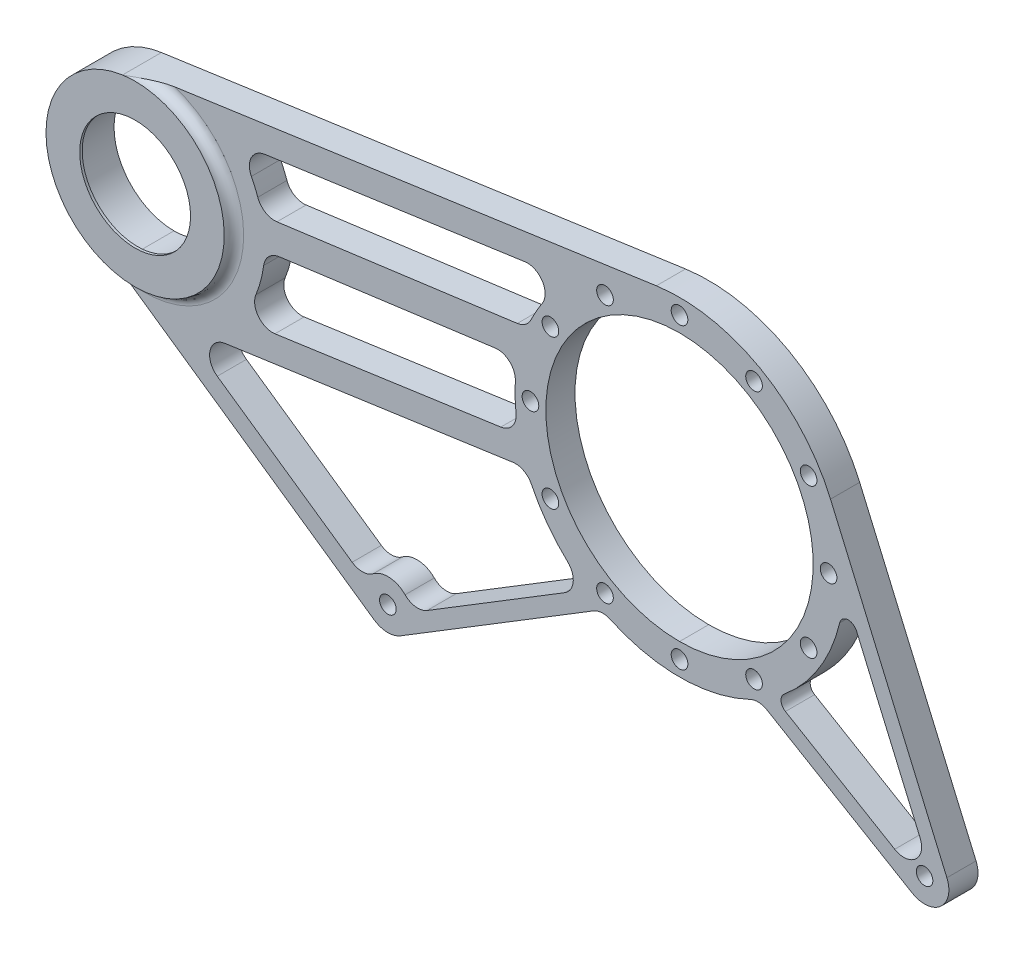
SolidWorks part; units mm, degrees
material "6061-T6 (SS)"
ref_plane "Front Plane" through (0, 0, 0) normal (0, 0, 1) x (1, 0, 0)
ref_plane "Top Plane" through (0, 0, 0) normal (0, 1, 0) x (1, 0, 0)
ref_plane "Right Plane" through (0, 0, 0) normal (1, 0, 0) x (0, 0, -1)
sketch "Sketch1" plane through (0, 0, 0) normal (0, 0, 1) x (1, 0, 0)
  line L0 (-328.7713, 136.1765) -> (-123.3819, 165.4094)
  line L1 (-343.7594, 72.9056) -> (-234.0298, -3.2296)
  line L2 (-223.6277, -3.528) -> (-148.0091, 42.7538)
  line L3 (-114.3, 88.9) -> (-114.3, 101.6) construction
  line L4 (-55.1193, 127.1299) -> (-9.5189, 21.4239)
  line L5 (-23.1153, 9.4535) -> (-80.0139, 43.1208)
  circle A0 centre (-114.3, 88.9) radius 82.9716 construction
  circle A1 centre (-228.6, -20.8038) radius 12.7 construction
  circle A2 centre (0, 0) radius 12.7 construction
  circle A3 centre (-323.85, 101.6) radius 114 construction
  circle A4 centre (-323.85, 101.6) radius 23.5
  circle A5 centre (-114.3, 101.6) radius 52.3875
  arc A6 (-141.4233, 43.1325) -> (-86.5756, 43.4151) centre (-114.3, 101.6) ccw
  circle A7 centre (-323.85, 101.6) radius 34.925
  arc A8 (-223.6277, -3.528) -> (-234.0298, -3.2296) centre (-228.6, 4.5962) cw
  arc A9 (-9.5189, 21.4239) -> (-23.1153, 9.4535) centre (-18.2648, 17.651) cw
  circle A10 centre (-228.6, 4.5962) radius 3.2512
  circle A11 centre (-18.2648, 17.651) radius 3.2512
  arc A12 (-141.4233, 43.1325) -> (-148.0091, 42.7538) centre (-144.3627, 36.7961) ccw
  arc A13 (-80.0139, 43.1208) -> (-86.5756, 43.4151) centre (-83.571, 37.1094) ccw
  arc A14 (-141.4233, 43.1325) -> (-86.5756, 43.4151) centre (-114.3, 101.6) ccw construction
  arc A15 (-123.3819, 165.4094) -> (-55.1193, 127.1299) centre (-114.3, 101.6) cw
  arc A16 (-141.4233, 43.1325) -> (-86.5756, 43.4151) centre (-114.3, 101.6) ccw
  arc A17 (-55.1193, 127.1299) -> (-123.3819, 165.4094) centre (-114.3, 101.6) ccw construction
  point P32 (0, 0)
  point P33 (0, 0)
  dimension "D1" = 88.9
  dimension "D2" = 12.7
  dimension "D3" = 25.4
  dimension "D4" = 25.4
  dimension "D8" = 165.9433
  dimension "D9" = 228
  dimension "D10" = 47
  dimension "D12" = 104.775
  dimension "D15" = 69.85
  dimension "D16" = 9.525
  dimension "D18" = 9.525
  dimension "D20" = 6.5024
  dimension "D21" = 6.5024
  dimension "D23" = 6.985
  dimension "D24" = 6.985
  dimension "D25" = 128.905
  dimension "D5" = 228.6
  dimension "D6" = 20.8038
  dimension "D7" = 114.3
  dimension "D11" = 12.7
  dimension "D13" = 209.55
  dimension "D17" = 25.4
  dimension "D19" = 25.4
  dimension "D22" = 17.651
extrude "Boss-Extrude1" add sketch "Sketch1" along normal blind 11.43 contours A7 A4 | A8 L2 A6 L0 A7 L1 A10 | A6 A5 | A9 L4 A6 L5 A11 region at (-188.8604, 80.9757, 0) region at (-301.6077, 127.2322, 0)
ref_point "Point2"
ref_point "Point4"
ref_plane "Plane2" through (-114.3, 0, 0) normal (1, 0, 0) x (0, 0, -1)
ref_plane "Plane3" through (-323.85, 0, 0) normal (1, 0, 0) x (0, 0, -1)
sketch "Sketch5" plane through (0, 0, 11.43) normal (0, 0, 1) x (1, 0, 0)
  circle A0 centre (-323.85, 101.6) radius 23.5
  circle A1 centre (-323.85, 101.6) radius 34.925
extrude "Boss-Extrude3" add sketch "Sketch5" along normal blind 3.81
fillet "Fillet2" radius 3.81 1 edges at (-289.8655, 93.5495, 11.43)
sketch "Sketch6" plane through (0, 0, 15.24) normal (0, 0, 1) x (1, 0, 0)
  circle A0 centre (-323.85, 101.6) radius 23.5
  circle A1 centre (-323.85, 101.6) radius 21.722
  dimension "D1" = 47
  dimension "D2" = 1.778
extrude "Boss-Extrude4" add sketch "Sketch6" against normal blind 0.9677
split line "Split Line3"
split line "Split Line4"
sketch "Sketch7" plane through (0, 0, 0) normal (0, 0, 1) x (1, 0, 0)
  line L0 (-276.8856, 133.299) -> (-174.9449, 147.8081)
  line L1 (-299.5603, 140.3341) -> (-125.0224, 165.1759)
  line L2 (-312.1859, 138.5371) -> (-123.3819, 165.4094) construction
  line L3 (-329.9956, 63.3556) -> (-234.0298, -3.2296) construction
  line L4 (-329.9956, 63.3556) -> (-319.5178, 56.0857) construction
  line L5 (-295.4693, 48.6743) -> (-242.5925, 11.9861)
  line L6 (-213.2408, 10.2742) -> (-159.2746, 43.3038)
  line L7 (-223.6277, -3.528) -> (-148.0091, 42.7538) construction
  line L8 (-223.6277, -3.528) -> (-148.0091, 42.7538) construction
  line L9 (-292.4716, 61.3285) -> (-179.5871, 77.3953)
  line L10 (-272.8543, 74.383) -> (-184.3367, 86.9817)
  line L11 (-29.9577, 20.8806) -> (-72.7896, 46.2245)
  line L12 (-19.9871, 29.6588) -> (-44.937, 87.4951)
  line L13 (-23.1153, 9.4535) -> (-80.0139, 43.1208) construction
  line L14 (-55.1193, 127.1299) -> (-9.5189, 21.4239) construction
  line L15 (-23.1153, 9.4535) -> (-80.0139, 43.1208) construction
  line L16 (-55.1193, 127.1299) -> (-9.5189, 21.4239) construction
  line L17 (-312.1859, 138.5371) -> (-123.3819, 165.4094) construction
  line L18 (-278.2115, 104.2679) -> (-178.0675, 117.6829) construction
  line L19 (-272.0734, 112.7782) -> (-177.8671, 125.3978)
  line L20 (-269.4316, 101.6) -> (-177.5668, 113.9059) construction
  line L22 (-186.5425, 112.7036) -> (-271.2809, 101.3523)
  circle A0 centre (-114.3, 101.6) radius 62.0284 construction
  circle A1 centre (-323.85, 101.6) radius 39.37 construction
  arc A4 (-292.4716, 61.3285) -> (-295.4693, 48.6743) centre (-291.4874, 54.4132) ccw
  arc A5 (-172.3155, 73.5228) -> (-158.1669, 54.379) centre (-114.3, 101.6) ccw
  arc A6 (-158.1669, 54.379) -> (-159.2746, 43.3038) centre (-162.9209, 49.2615) cw
  arc A7 (-179.5871, 77.3953) -> (-172.3155, 73.5228) centre (-178.6029, 70.48) cw
  arc A8 (-282.1065, 123.1764) -> (-279.5813, 117.3588) centre (-323.85, 101.6) cw
  arc A9 (-168.1271, 137.0509) -> (-172.4884, 129.3171) centre (-114.3, 101.6) ccw
  arc A10 (-178.3767, 94.6501) -> (-184.3367, 86.9817) centre (-185.321, 93.897) cw
  arc A11 (-282.1065, 123.1764) -> (-276.8856, 133.299) centre (-275.9014, 126.3837) cw
  arc A12 (-280.3106, 83.9256) -> (-272.8543, 74.383) centre (-273.8386, 81.2983) ccw
  arc A13 (-174.9449, 147.8081) -> (-168.1271, 137.0509) centre (-173.9606, 140.8928) cw
  arc A14 (-221.8426, 11.3091) -> (-234.3754, 12.1705) centre (-228.6, 4.5962) ccw
  arc A15 (-223.6277, -3.528) -> (-223.0453, -3.1415) centre (-228.6, 4.5962) ccw
  arc A16 (-234.3754, 12.1705) -> (-242.5925, 11.9861) centre (-238.6106, 17.725) cw
  arc A17 (-213.2408, 10.2742) -> (-221.8426, 11.3091) centre (-216.8872, 16.2319) cw
  arc A19 (-19.9871, 29.6588) -> (-29.9577, 20.8806) centre (-26.4007, 26.892) cw
  arc A20 (-73.2362, 51.9221) -> (-51.5444, 86.9079) centre (-114.3, 101.6) ccw
  arc A21 (-44.937, 87.4951) -> (-51.5444, 86.9079) centre (-48.1438, 86.1117) ccw
  arc A22 (-72.7896, 46.2245) -> (-73.2362, 51.9221) centre (-71.0111, 49.2302) cw
  arc A23 (-177.5668, 113.9059) -> (-173.9892, 125.9173) centre (-114.3, 101.6) ccw construction
  arc A24 (-277.2765, 95.3571) -> (-280.3106, 83.9256) centre (-323.85, 101.6) cw
  arc A25 (-178.642, 105.3717) -> (-178.3767, 94.6501) centre (-114.3, 101.6) ccw
  arc A26 (-172.4884, 129.3171) -> (-177.8671, 125.3978) centre (-178.7945, 132.3209) cw
  arc A27 (-178.642, 105.3717) -> (-186.5425, 112.7036) centre (-185.6151, 105.7804) ccw
  arc A28 (-272.0734, 112.7782) -> (-279.5813, 117.3588) centre (-273.0008, 119.7014) cw
  arc A29 (-271.2809, 101.3523) -> (-277.2765, 95.3571) centre (-270.3535, 94.4291) ccw
  point P31 (-310.0925, 58.8205)
  point P33 (-172.4396, 79.9826)
  point P41 (-287.8037, 131.745)
  point P45 (-154.09, 149.1844)
  point P64 (-78.8001, 50.7347)
  dimension "D3" = 7.62
  dimension "D5" = 46.99
  dimension "D6" = 124.0568
  dimension "D7" = 6.985
  dimension "D8" = 6.985
  dimension "D10" = 6.985
  dimension "D11" = 9.525
  dimension "D12" = 6.985
  dimension "D13" = 6.985
  dimension "D16" = 3.4925
  dimension "D17" = 128.905
  dimension "D22" = 6.985
  dimension "D2" = 10.16
  dimension "D4" = 6.35
  dimension "D9" = 10.16
  dimension "D14" = 6.35
  dimension "D15" = 6.35
  dimension "D18" = 3.81
  dimension "D19" = 11.43
  dimension "D20" = 0.471
  dimension "D21" = 101.0385
extrude "Cut-Extrude2" cut sketch "Sketch7" against normal through all both and the other way through all contours A17 L6 A6 A5 A7 L9 A4 L5 A16 A14 | A13 L0 A11 A8 A12 L10 A10 A9 | A22 L11 A19 L12 A21 A20 | A21 A20 A22 L11 A19 L12 | A29 L22 A27 A25 A10 L10 A12 A24 region at (-224.7389, 130.0943, 0) region at (-223.2656, 45.8331, 0) region at (-45.2882, 50.8908, 0)
sketch "Sketch8" plane through (0, 0, 11.43) normal (0, 0, 1) x (1, 0, 0)
  line L0 (-114.3, 101.6) -> (-114.3, 160.02) construction
  circle A20 centre (-114.3, 101.6) radius 58.42 construction
  circle A21 centre (-114.3, 160.02) radius 3.2639
  circle A22 centre (-85.09, 152.1932) radius 3.2639
  circle A23 centre (-63.7068, 130.81) radius 3.2639
  circle A24 centre (-55.88, 101.6) radius 3.2639
  circle A25 centre (-63.7068, 72.39) radius 3.2639
  circle A26 centre (-85.09, 51.0068) radius 3.2639
  circle A27 centre (-114.3, 43.18) radius 3.2639
  circle A28 centre (-143.51, 51.0068) radius 3.2639
  circle A29 centre (-164.8932, 72.39) radius 3.2639
  circle A30 centre (-172.72, 101.6) radius 3.2639
  circle A31 centre (-164.8932, 130.81) radius 3.2639
  circle A32 centre (-143.51, 152.1932) radius 3.2639
  point P22 (-114.3, 101.6)
  point P31 (-112.8188, 101.2031)
  point P32 (-114.3, 101.6)
  dimension "D1" = 116.84
  dimension "D2" = 6.5278
  dimension "D3" = 12
extrude "Cut-Extrude3" cut sketch "Sketch8" against normal through all both and the other way through all
